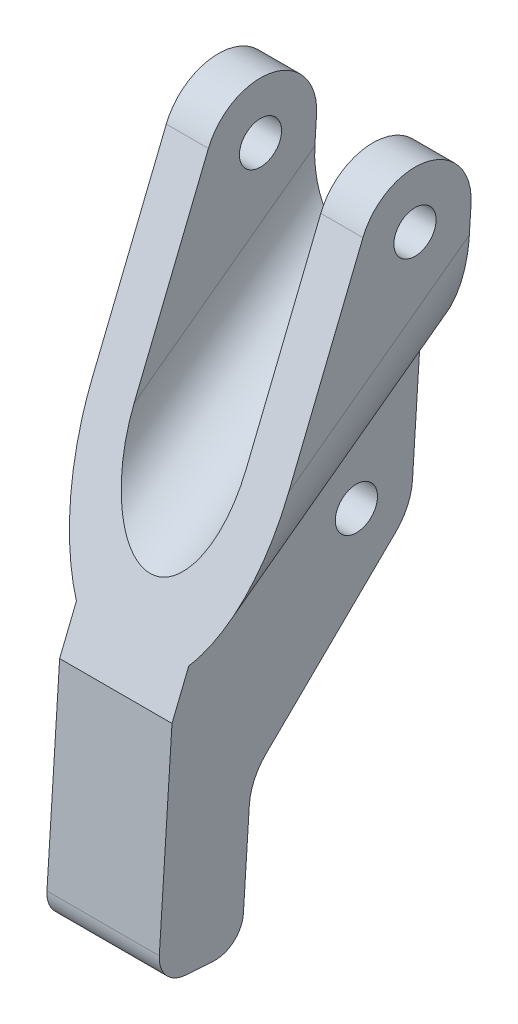
SolidWorks part; units mm, degrees
ref_plane "前视基准面" through (0, 0, 0) normal (0, 0, 1) x (1, 0, 0)
ref_plane "上视基准面" through (0, 0, 0) normal (0, 1, 0) x (1, 0, 0)
ref_plane "右视基准面" through (0, 0, 0) normal (1, 0, 0) x (0, 0, -1)
sketch "草图1" plane through (0, 0, 0) normal (1, 0, 0) x (0, 0, -1)
  line L0 (0, 60) -> (0, 0) construction
  line L1 (0, 0) -> (-67.3251, 0) construction
  line L2 (0, 60) -> (-30, 60) construction
  line L3 (-5, 25) -> (-5, 0) construction
  line L4 (-5, 25) -> (-39.7252, 44.8534) construction
  line L5 (-39.7252, 44.8534) -> (-64.896, 28.5307) construction
  line L6 (-64.896, 28.5307) -> (-5, 25) construction
  line L7 (-39.7252, 44.8534) -> (-30, 60) construction
  line L8 (-30, 60) -> (-30, 68) construction
  line L9 (-63.7258, 46.4926) -> (-64.896, 28.5307) construction
  line L10 (-63.7258, 46.4926) -> (-78.0255, 21.8396) construction
  line L11 (-78.0255, 21.8396) -> (-79.0596, 5.9666) construction
  line L12 (-79.0596, 5.9666) -> (-73.0723, 5.5766) construction
  line L13 (-73.0723, 5.5766) -> (-72.4222, 15.5554) construction
  line L14 (-72.4222, 15.5554) -> (-64.896, 28.5307) construction
  line L15 (-30, 68) -> (-63.7258, 46.4926) construction
  line L16 (-59.7343, 46.2325) -> (-60.9045, 28.2706)
  line L17 (-67.4333, 47.9941) -> (-78.0255, 21.8396)
  line L18 (-78.0255, 21.8396) -> (-79.0596, 5.9666)
  line L19 (-79.0596, 5.9666) -> (-73.0723, 5.5766)
  line L20 (-73.0723, 5.5766) -> (-72.4222, 15.5554)
  line L21 (-72.4222, 15.5554) -> (-62.0964, 25.6737)
  circle A0 centre (-64.896, 28.5307) radius 1.5
  circle A1 centre (-63.7258, 46.4926) radius 1.5
  arc A2 (-62.0964, 25.6737) -> (-60.9045, 28.2706) centre (-64.896, 28.5307) ccw
  arc A3 (-59.7343, 46.2325) -> (-67.4333, 47.9941) centre (-63.7258, 46.4926) ccw
  dimension "D9" = 3
  dimension "D18" = 3
  dimension "D19" = 8
  dimension "D1" = 50
  dimension "D2" = 5
  dimension "D3" = 18
  dimension "D4" = 6
  dimension "D5" = 8
  dimension "D6" = 120
  dimension "D7" = 30
  dimension "D8" = 18
  dimension "D10" = 30
  dimension "D11" = 40
  dimension "D12" = 60
  dimension "D13" = 15
  dimension "D14" = 10
  dimension "D15" = 11.1531
  dimension "D16" = 8
  dimension "D17" = 40
extrude "凸台-拉伸1" add sketch "草图1" along normal mid plane 8
fillet "圆角1" radius 2 2 edges at (0, 5.9666, 79.0596) (0, 5.5766, 73.0723)
fillet "圆角2" radius 4 1 edges at (0, 15.5554, 72.4222)
sketch "草图2" plane through (0, 0, 0) normal (1, 0, 0) x (0, 0, -1)
  line L0 (-60.9045, 28.2706) -> (-59.7343, 46.2325) construction
  line L1 (-67.4333, 47.9941) -> (-78.0255, 21.8396) construction
  line L2 (-60.5345, 33.9501) -> (-59.7343, 46.2325)
  line L3 (-67.4333, 47.9941) -> (-78.0255, 21.8396)
  line L4 (-78.0751, 21.0782) -> (-60.5345, 33.9501)
  line L5 (-78.0255, 21.8396) -> (-78.9296, 7.9624) construction
  line L6 (-78.0255, 21.8396) -> (-78.0751, 21.0782)
  circle A0 centre (-63.7258, 46.4926) radius 1.5 construction
  arc A1 (-59.7343, 46.2325) -> (-67.4333, 47.9941) centre (-63.7258, 46.4926) ccw construction
  circle A2 centre (-63.7258, 46.4926) radius 1.5
  arc A3 (-59.7343, 46.2325) -> (-67.4333, 47.9941) centre (-63.7258, 46.4926) ccw
  dimension "D1" = 12
  dimension "D2" = 130
extrude "凸台-拉伸2" add sketch "草图2" along normal mid plane 14
ref_plane "基准面1" through (0, -12.3095, 16.7742) normal (0, -0.5916, 0.8062) x (-1, 0, 0)
sketch "草图3" plane through (0, 76.4939, 81.9411) normal (0, -0.5916, 0.8062) x (-1, 0, 0)
  line L0 (-7, 37.5352) -> (-7, 30.9641) construction
  line L13 (-7, 37.5352) -> (-7, 30.9641) construction
  line L14 (7, 30.9641) -> (7, 37.5352) construction
  line L15 (7, 30.9641) -> (7, 37.5352) construction
  line L16 (-7, 30.9641) -> (7, 30.9641) construction
  line L17 (0, 30.9641) -> (0, 38.9641) construction
  line L18 (4, 38.9641) -> (4, 30.9641)
  line L19 (4, 30.9641) -> (-4, 30.9641)
  line L20 (-4, 30.9641) -> (-4, 38.9641)
  line L21 (7, 38.9641) -> (7, 53.9641)
  line L22 (7, 46.9641) -> (7, 37.5352) construction
  line L23 (7, 53.9641) -> (4, 53.9641)
  line L24 (4, 53.9641) -> (4, 44.7086)
  line L25 (4, 51.324) -> (4, 46.9641) construction
  line L26 (-4, 53.9641) -> (-4, 44.7086)
  line L27 (-7, 53.9641) -> (-4, 53.9641)
  line L28 (-7, 38.9641) -> (-7, 53.9641)
  arc A3 (4, 38.9641) -> (-4, 38.9641) centre (0, 38.9641) ccw
  arc A4 (7, 38.9641) -> (4, 44.7086) centre (0, 38.9641) ccw
  arc A5 (-7, 38.9641) -> (-4, 44.7086) centre (0, 38.9641) cw
  dimension "D1" = 8
  dimension "D3" = 15
  dimension "D2" = 8
extrude "切除-拉伸1" cut sketch "草图3" along normal through all both and the other way through all
sketch "草图4" plane through (0, 0, 0) normal (1, 0, 0) x (0, 0, -1)
  line L0 (-68.896, 28.5307) -> (-68.896, 30.6117)
  line L1 (-72.2258, 28.1682) -> (-75.0633, 21.1618)
  line L2 (-75.0633, 21.1618) -> (-76.0659, 5.7716)
  line L4 (-78.0255, 21.8396) -> (-78.9296, 7.9624) construction
  line L5 (-76.8312, 24.7886) -> (-78.0255, 21.8396) construction
  line L7 (-78.0255, 21.8396) -> (-78.9296, 7.9624)
  line L8 (-77.0638, 5.8366) -> (-75.068, 5.7066)
  line L9 (-72.9423, 7.5723) -> (-72.5216, 14.029)
  line L10 (-71.3296, 16.626) -> (-62.0964, 25.6737)
  line L11 (-60.9045, 28.2706) -> (-60.3431, 36.8881)
  line L12 (-60.3431, 36.8881) -> (-76.8312, 24.7886)
  line L13 (-76.8312, 24.7886) -> (-78.0255, 21.8396)
  line L15 (-76.0659, 5.7716) -> (-75.068, 5.7066)
  line L16 (-72.9423, 7.5723) -> (-72.5216, 14.029)
  line L17 (-71.3296, 16.626) -> (-62.0964, 25.6737)
  line L19 (-68.896, 30.6117) -> (-72.2258, 28.1682)
  arc A0 (-68.896, 28.5307) -> (-62.0964, 25.6737) centre (-64.896, 28.5307) ccw
  arc A4 (-78.9296, 7.9624) -> (-77.0638, 5.8366) centre (-76.9338, 7.8324) ccw
  arc A5 (-75.068, 5.7066) -> (-72.9423, 7.5723) centre (-74.938, 7.7024) ccw
  arc A6 (-71.3296, 16.626) -> (-72.5216, 14.029) centre (-68.5301, 13.769) ccw
  arc A7 (-62.0964, 25.6737) -> (-60.9045, 28.2706) centre (-64.896, 28.5307) ccw
  arc A9 (-75.068, 5.7066) -> (-72.9423, 7.5723) centre (-74.938, 7.7024) ccw
  arc A10 (-71.3296, 16.626) -> (-72.5216, 14.029) centre (-68.5301, 13.769) ccw
  dimension "D2" = 3
  dimension "D3" = 3
  dimension "D1" = 0
extrude "切除-拉伸2" cut sketch "草图4" against normal mid plane 4
fillet "圆角3" radius 1 4 edges at (0, 5.7716, 76.0659) (0, 21.1618, 75.0633) (0, 28.1682, 72.2258) (0, 30.6117, 68.896)
